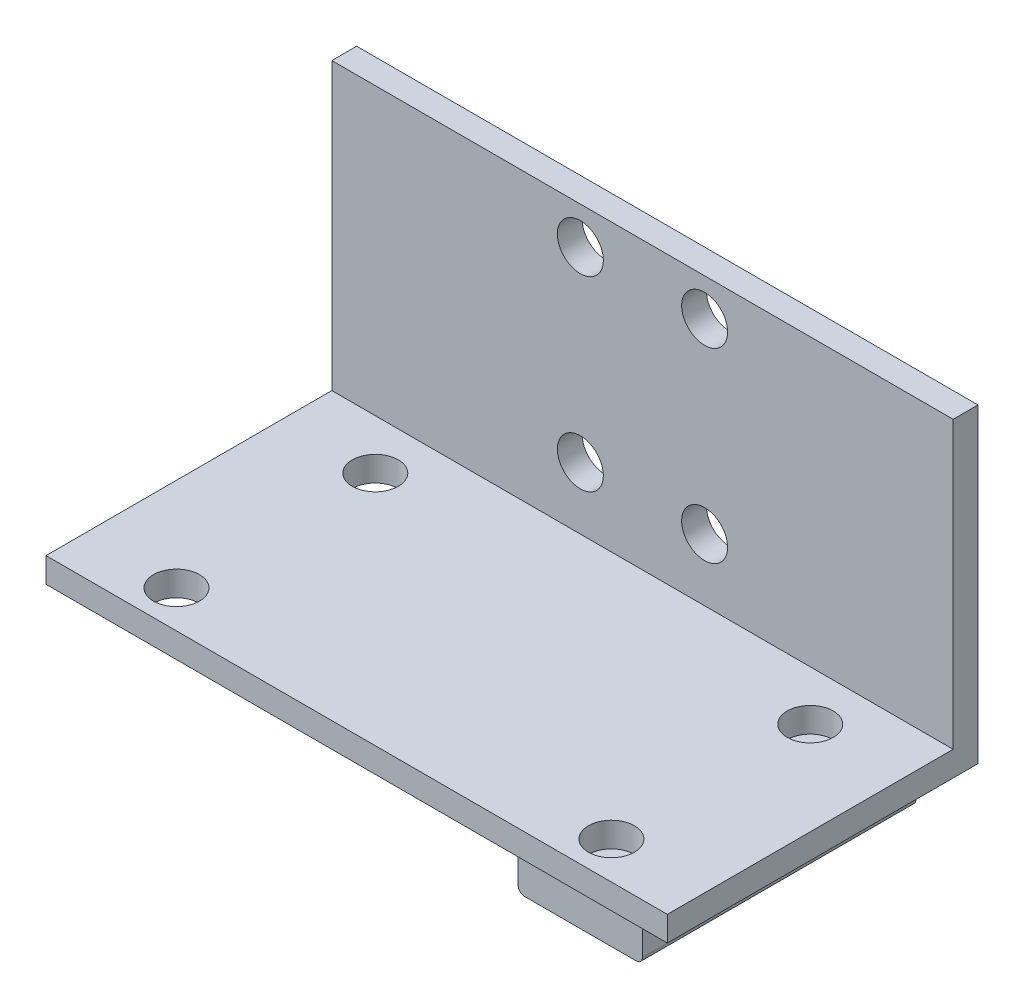
SolidWorks part; units mm, degrees
ref_plane "Front Plane" through (0, 0, 0) normal (0, 0, 1) x (1, 0, 0)
ref_plane "Top Plane" through (0, 0, 0) normal (0, 1, 0) x (1, 0, 0)
ref_plane "Right Plane" through (0, 0, 0) normal (1, 0, 0) x (0, 0, -1)
sketch "Sketch1" plane through (0, 0, 0) normal (0, 1, 0) x (1, 0, 0)
  line L1 (0, 0) -> (50, 0)
  line L2 (0, 0) -> (0, 25)
  line L3 (0, 25) -> (50, 25)
  line L4 (50, 0) -> (50, 25)
  dimension "D1" = 50
  dimension "D2" = 25
extrude "Boss-Extrude1" add sketch "Sketch1" along normal blind 2
sketch "Sketch3" plane through (0, 2, 0) normal (0, 1, 0) x (1, 0, 0)
  line L0 (50, 25) -> (0, 25) construction
  line L1 (0, 25) -> (50, 25)
  line L2 (0, 25) -> (0, 23)
  line L3 (0, 23) -> (50, 23)
  line L4 (50, 25) -> (50, 23)
  line L5 (50, 0) -> (50, 25) construction
  dimension "D1" = 2
extrude "Boss-Extrude2" add sketch "Sketch3" along normal blind 23
sketch "Sketch4" plane through (0, 0, -23) normal (0, 0, 1) x (1, 0, 0)
  line L0 (25, 25) -> (25, 2) construction
  line L1 (0, 25) -> (50, 25) construction
  line L2 (0, 2) -> (50, 2) construction
  circle A0 centre (20, 22) radius 1.85
  circle A1 centre (30, 22) radius 1.85
  circle A2 centre (30, 7) radius 1.85
  circle A3 centre (20, 7) radius 1.85
  point P8 (0, 0)
  dimension "D1" = 3.7
  dimension "D2" = 3.7
  dimension "D3" = 3.7
  dimension "D4" = 3.7
  dimension "D5" = 15
  dimension "D6" = 10
  dimension "D7" = 3
extrude "Cut-Extrude1" cut sketch "Sketch4" against normal blind 23
sketch "Sketch5" plane through (0, 2, 0) normal (0, 1, 0) x (1, 0, 0)
  line L0 (0, 0) -> (50, 0) construction
  line L1 (25, 23) -> (25, 0) construction
  line L2 (0, 23) -> (50, 23) construction
  circle A0 centre (7.5, 3) radius 1.85
  circle A1 centre (7.5, 19) radius 1.85
  circle A2 centre (42.5, 3) radius 1.85
  circle A3 centre (42.5, 19) radius 1.85
  point P8 (0, 0)
  dimension "D1" = 3.7
  dimension "D2" = 3.7
  dimension "D3" = 3.7
  dimension "D4" = 3.7
  dimension "D5" = 16
  dimension "D6" = 3
  dimension "D7" = 35
extrude "Cut-Extrude2" cut sketch "Sketch5" against normal blind 23
sketch "Sketch6" plane through (0, 0, 0) normal (0, -1, 0) x (1, 0, 0)
  line L0 (42.5, -20.85) -> (42.5, -12.2066) construction
  line L1 (47.5, -22.5) -> (37.5, -22.5)
  line L2 (47.5, -22.5) -> (47.5, -0.5)
  line L3 (47.5, -0.5) -> (37.5, -0.5)
  line L4 (37.5, -22.5) -> (37.5, -0.5)
  line L7 (50, -25) -> (0, -25) construction
  circle A0 centre (42.5, -19) radius 1.85 construction
  dimension "D1" = 10
  dimension "D2" = 22
  dimension "D3" = 2.5
extrude "Boss-Extrude3" add sketch "Sketch6" along normal blind 3
fillet "Fillet1" radius 0.5 2 edges at (47.5, -3, -11.5) (37.5, -3, -11.5)
